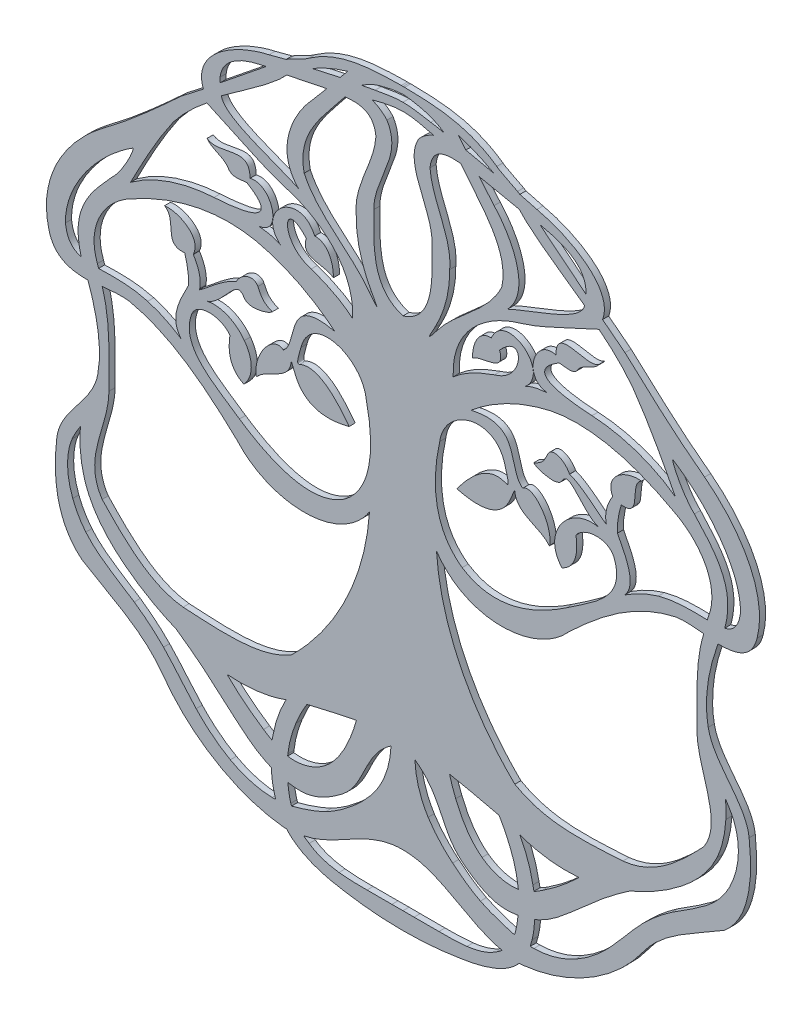
SolidWorks part; units mm, degrees
ref_plane "Front Plane" through (0, 0, 0) normal (0, 0, 1) x (1, 0, 0)
ref_plane "Top Plane" through (0, 0, 0) normal (0, 1, 0) x (1, 0, 0)
ref_plane "Right Plane" through (0, 0, 0) normal (1, 0, 0) x (0, 0, -1)
sketch "Sketch2" plane through (0, 0, 0) normal (0, 0, 1) x (1, 0, 0)
  line L0 (124.0467, 202.4567) -> (123.8762, 202.5007)
  line L1 (91.3206, 170.146) -> (91.46, 169.8814)
  line L2 (105.8644, 182.4526) -> (105.9481, 182.5183)
  line L3 (129.2501, 171.0909) -> (129.9283, 171.2663)
  line L4 (97.8903, 196.5004) -> (97.9848, 196.5477)
  line L5 (83.0151, 199.9226) -> (82.9279, 199.854)
  line L6 (67.6817, 189.4453) -> (67.9, 189.9835)
  line L7 (65.2474, 200.7194) -> (65.1856, 200.833)
  line L8 (61.6055, 199.6125) -> (61.6703, 199.4023)
  line L9 (180.5533, 202.4567) -> (180.7238, 202.5007)
  line L10 (213.2794, 170.146) -> (213.14, 169.8814)
  line L11 (198.7355, 182.4526) -> (198.6519, 182.5183)
  line L12 (175.3499, 171.0909) -> (174.6717, 171.2663)
  line L13 (206.7097, 196.5004) -> (206.6152, 196.5477)
  line L14 (221.5087, 199.9226) -> (221.5309, 199.9004)
  line L15 (236.8537, 189.6047) -> (236.6999, 189.9835)
  line L16 (239.3526, 200.7194) -> (239.4144, 200.833)
  line L17 (242.9945, 199.6125) -> (242.9297, 199.4023)
  line L18 (151.6258, 304.818) -> (152.3, 304.7699)
  line L19 (152.3, 304.7699) -> (152.9742, 304.818)
  line L20 (152.3, 8.2515) -> (147.7055, 8.2281)
  line L21 (156.8944, 8.2281) -> (152.3, 8.2515)
  line L22 (112.4054, 62.5359) -> (113.271, 62.7419)
  line L23 (192.1946, 62.5359) -> (191.329, 62.7419)
  spline S0 degree 3 poles (131.4175, 210.6535) (132.3447, 228.4153) (118.3052, 239.7229) (103.4832, 244.0034) knots 0 0 0 0 1 1 1 1
  spline S1 degree 3 poles (103.4832, 244.0034) (95.1251, 246.4171) (85.7701, 251.4597) (70.8553, 258.1318) knots 0 0 0 0 1 1 1 1
  spline S2 degree 3 poles (70.8553, 258.1318) (65.6236, 253.9512) (60.9556, 249.561) (56.9117, 244.3367) knots 0 0 0 0 1 1 1 1
  spline S3 degree 3 poles (56.9117, 244.3367) (50.1323, 234.6888) (44.4951, 224.0798) (39.129, 213.7146) knots 0 0 0 0 1 1 1 1
  spline S4 degree 3 poles (39.129, 213.7146) (49.1167, 221.0722) (61.6984, 224.9258) (73.7861, 225.6047) knots 0 0 0 0 1 1 1 1
  spline S5 degree 3 poles (73.7861, 225.6047) (81.1714, 226.0581) (104.1841, 227.716) (87.4693, 237.7349) knots 0 0 0 0 1 1 1 1
  spline S6 degree 3 poles (87.4693, 237.7349) (84.9969, 237.7465) (81.3851, 236.3748) (79.7778, 239.034) knots 0 0 0 0 1 1 1 1
  spline S7 degree 3 poles (79.7778, 239.034) (77.8345, 242.2491) (72.9741, 242.3849) (70.9297, 245.4413) knots 0 0 0 0 1 1 1 1
  spline S8 degree 3 poles (70.9297, 245.4413) (76.4954, 241.6186) (88.6993, 251.6059) (88.7661, 239.9743) knots 0 0 0 0 1 1 1 1
  spline S9 degree 3 poles (88.7661, 239.9743) (98.0513, 242.3534) (102.8069, 225.5) (92.2542, 224.5881) knots 0 0 0 0 1 1 1 1
  spline S10 degree 3 poles (92.2542, 224.5881) (95.4523, 224.2265) (98.8012, 223.862) (101.5143, 222.2107) knots 0 0 0 0 1 1 1 1
  spline S11 degree 3 poles (101.5143, 222.2107) (90.479, 231.7857) (109.6509, 246.2092) (115.6231, 232.6458) knots 0 0 0 0 1 1 1 1
  spline S12 degree 3 poles (115.6231, 232.6458) (121.3356, 232.927) (123.5816, 226.159) (123.3677, 221.4698) knots 0 0 0 0 1 1 1 1
  spline S13 degree 3 poles (123.3677, 221.4698) (119.7643, 224.5708) (109.41, 222.0646) (112.1698, 229.9921) knots 0 0 0 0 1 1 1 1
  spline S14 degree 3 poles (112.1698, 229.9921) (101.6543, 241.7817) (101.1203, 223.5384) (114.195, 220.0791) knots 0 0 0 0 1 1 1 1
  spline S15 degree 3 poles (114.195, 220.0791) (120.2811, 217.956) (126.7166, 215.0066) (131.5266, 210.6535) knots 0 0 0 0 1 1 1 1
  spline S16 degree 3 poles (173.1824, 210.6535) (172.2553, 228.4153) (186.2948, 239.7229) (201.1168, 244.0034) knots 0 0 0 0 1 1 1 1
  spline S17 degree 3 poles (201.1168, 244.0034) (209.4748, 246.4171) (218.8299, 251.4597) (233.7447, 258.1318) knots 0 0 0 0 1 1 1 1
  spline S18 degree 3 poles (233.7447, 258.1318) (238.9764, 253.9512) (243.6444, 249.561) (247.6883, 244.3367) knots 0 0 0 0 1 1 1 1
  spline S19 degree 3 poles (247.6883, 244.3367) (254.4677, 234.6888) (260.1049, 224.0798) (265.471, 213.7146) knots 0 0 0 0 1 1 1 1
  spline S20 degree 3 poles (265.471, 213.7146) (255.4833, 221.0722) (242.9016, 224.9258) (230.8139, 225.6047) knots 0 0 0 0 1 1 1 1
  spline S21 degree 3 poles (230.8139, 225.6047) (223.4286, 226.0581) (200.4159, 227.716) (217.1307, 237.7349) knots 0 0 0 0 1 1 1 1
  spline S22 degree 3 poles (217.1307, 237.7349) (219.6031, 237.7465) (223.2149, 236.3748) (224.8222, 239.034) knots 0 0 0 0 1 1 1 1
  spline S23 degree 3 poles (224.8222, 239.034) (226.7655, 242.2491) (231.6259, 242.3849) (233.6703, 245.4413) knots 0 0 0 0 1 1 1 1
  spline S24 degree 3 poles (233.6703, 245.4413) (228.1035, 241.6202) (215.9024, 251.6108) (215.8324, 239.9793) knots 0 0 0 0 1 1 1 1
  spline S25 degree 3 poles (215.8324, 239.9793) (206.5437, 242.3451) (201.8124, 225.4848) (212.3663, 224.5881) knots 0 0 0 0 1 1 1 1
  spline S26 degree 3 poles (212.3663, 224.5881) (209.1674, 224.2336) (205.8177, 223.8766) (203.101, 222.2314) knots 0 0 0 0 1 1 1 1
  spline S27 degree 3 poles (203.101, 222.2314) (214.1222, 231.8225) (194.9292, 246.218) (188.9769, 232.6458) knots 0 0 0 0 1 1 1 1
  spline S28 degree 3 poles (188.9769, 232.6458) (183.2643, 232.927) (181.0184, 226.159) (181.2323, 221.4698) knots 0 0 0 0 1 1 1 1
  spline S29 degree 3 poles (181.2323, 221.4698) (184.8357, 224.5708) (195.19, 222.0646) (192.4302, 229.9921) knots 0 0 0 0 1 1 1 1
  spline S30 degree 3 poles (192.4302, 229.9921) (202.9457, 241.7817) (203.4797, 223.5384) (190.405, 220.0791) knots 0 0 0 0 1 1 1 1
  spline S31 degree 3 poles (190.405, 220.0791) (184.3189, 217.956) (177.8834, 215.0066) (173.0734, 210.6535) knots 0 0 0 0 1 1 1 1
  spline S32 degree 3 poles (114.4335, 280.8354) (115.6926, 282.4321) (119.3612, 286.6279) (120.6433, 288.1846) knots 0 0 0 0 1 1 1 1
  spline S33 degree 3 poles (120.6433, 288.1846) (117.8502, 287.7388) (114.652, 286.9648) (111.6581, 286.3466) knots 0 0 0 0 1 1 1 1
  spline S34 degree 2 poles (111.6581, 286.3466) (109.0976, 285.8179) (103.9796, 284.7463) knots 0 0 0 1 1 1
  spline S35 degree 2 poles (103.9796, 284.7463) (101.9501, 282.7285) (101.0624, 281.7946) knots 0 0 0 1 1 1
  spline S36 degree 3 poles (101.0624, 281.7946) (93.5217, 275.03) (84.9819, 269.7463) (76.8684, 263.7279) knots 0 0 0 0 1 1 1 1
  spline S37 degree 3 poles (76.8684, 263.7279) (78.1012, 256.7056) (99.1504, 251.0771) (108.8436, 246.3864) knots 0 0 0 0 1 1 1 1
  spline S38 degree 3 poles (108.8436, 246.3864) (99.0563, 256.4976) (106.313, 272.0893) (114.4335, 280.8354) knots 0 0 0 0 1 1 1 1
  spline S39 degree 3 poles (190.1664, 280.8354) (188.9074, 282.4321) (185.2388, 286.6279) (183.9567, 288.1846) knots 0 0 0 0 1 1 1 1
  spline S40 degree 3 poles (183.9567, 288.1846) (186.7498, 287.7388) (189.948, 286.9648) (192.9419, 286.3466) knots 0 0 0 0 1 1 1 1
  spline S41 degree 2 poles (192.9419, 286.3466) (195.5024, 285.8179) (200.6204, 284.7463) knots 0 0 0 1 1 1
  spline S42 degree 2 poles (200.6204, 284.7463) (202.6498, 282.7285) (203.5376, 281.7946) knots 0 0 0 1 1 1
  spline S43 degree 3 poles (203.5376, 281.7946) (211.0783, 275.03) (219.6181, 269.7463) (227.7317, 263.7279) knots 0 0 0 0 1 1 1 1
  spline S44 degree 3 poles (227.7317, 263.7279) (226.4988, 256.7056) (205.4496, 251.0771) (195.7564, 246.3864) knots 0 0 0 0 1 1 1 1
  spline S45 degree 3 poles (195.7564, 246.3864) (205.5437, 256.4976) (198.287, 272.0893) (190.1664, 280.8354) knots 0 0 0 0 1 1 1 1
  spline S46 degree 3 poles (129.3371, 298.7606) (124.328, 297.3007) (119.1122, 295.0858) (114.5869, 292.4347) knots 0 0 0 0 1 1 1 1
  spline S47 degree 3 poles (114.5869, 292.4347) (114.6743, 292.3899) (114.9619, 292.4909) (115.0634, 292.5134) knots 0 0 0 0 1 1 1 1
  spline S48 degree 3 poles (115.0634, 292.5134) (118.7134, 293.3211) (122.4339, 294.1357) (126.1731, 294.9789) knots 0 0 0 0 1 1 1 1
  spline S49 degree 3 poles (126.1731, 294.9789) (127.3382, 296.4139) (128.2034, 297.377) (129.3371, 298.7606) knots 0 0 0 0 1 1 1 1
  spline S50 degree 3 poles (175.2629, 298.7606) (180.272, 297.3007) (185.4878, 295.0858) (190.0131, 292.4347) knots 0 0 0 0 1 1 1 1
  spline S51 degree 3 poles (190.0131, 292.4347) (189.9257, 292.3899) (189.6381, 292.4909) (189.5365, 292.5134) knots 0 0 0 0 1 1 1 1
  spline S52 degree 3 poles (189.5365, 292.5134) (185.8866, 293.3211) (182.1661, 294.1357) (178.4269, 294.9789) knots 0 0 0 0 1 1 1 1
  spline S53 degree 3 poles (178.4269, 294.9789) (177.2618, 296.4139) (176.3966, 297.377) (175.2629, 298.7606) knots 0 0 0 0 1 1 1 1
  spline S54 degree 3 poles (152.3, 299.1254) (148.3241, 299.1244) (144.6166, 298.3006) (140.731, 297.6643) knots 0 0 0 0 1 1 1 1
  spline S55 degree 3 poles (140.731, 297.6643) (138.8136, 297.3503) (136.9533, 297.0896) (135.1322, 296.6129) knots 0 0 0 0 1 1 1 1
  spline S56 degree 3 poles (135.1322, 296.6129) (137.3724, 298.1704) (139.9061, 299.5052) (142.8771, 300.2975) knots 0 0 0 0 1 1 1 1
  spline S57 degree 3 poles (142.8771, 300.2975) (145.4603, 300.9863) (149.2794, 301.9033) (152.3, 301.9499) knots 0 0 0 0 1 1 1 1
  spline S58 degree 3 poles (152.3, 301.9499) (155.3206, 301.9033) (159.1397, 300.9863) (161.7229, 300.2975) knots 0 0 0 0 1 1 1 1
  spline S59 degree 3 poles (161.7229, 300.2975) (164.6939, 299.5052) (167.2275, 298.1704) (169.4678, 296.6129) knots 0 0 0 0 1 1 1 1
  spline S60 degree 3 poles (169.4678, 296.6129) (167.6467, 297.0896) (165.7864, 297.3503) (163.869, 297.6643) knots 0 0 0 0 1 1 1 1
  spline S61 degree 3 poles (163.869, 297.6643) (159.9834, 298.3006) (156.2759, 299.1244) (152.3, 299.1254) knots 0 0 0 0 1 1 1 1
  spline S62 degree 2 poles (127.5425, 288.1624) (128.1065, 289.0471) (128.5638, 289.0858) knots 0 0 0 1 1 1
  spline S63 degree 3 poles (128.5638, 289.0858) (133.4843, 289.5017) (140.2137, 289.6551) (141.0643, 281.1364) knots 0 0 0 0 1 1 1 1
  spline S64 degree 3 poles (141.0643, 281.1364) (140.1847, 269.7923) (131.7735, 260.4078) (132.895, 248.5982) knots 0 0 0 0 1 1 1 1
  spline S65 degree 3 poles (132.895, 248.5982) (132.7464, 240.2776) (135.0817, 232.1131) (139.0246, 224.7742) knots 0 0 0 0 1 1 1 1
  spline S66 degree 3 poles (139.0246, 224.7742) (139.9951, 222.9677) (140.9599, 221.4257) (141.503, 220.1266) knots 0 0 0 0 1 1 1 1
  spline S67 degree 3 poles (141.503, 220.1266) (140.3841, 220.9726) (138.7592, 223.2318) (138.373, 223.7558) knots 0 0 0 0 1 1 1 1
  spline S68 degree 3 poles (138.373, 223.7558) (130.4207, 234.5457) (117.0074, 240.7506) (111.2689, 253.0797) knots 0 0 0 0 1 1 1 1
  spline S69 degree 3 poles (111.2689, 253.0797) (108.114, 267.1941) (119.5485, 277.7332) (127.5425, 288.1624) knots 0 0 0 0 1 1 1 1
  spline S70 degree 2 poles (177.0575, 288.1624) (176.4935, 289.0471) (176.0362, 289.0858) knots 0 0 0 1 1 1
  spline S71 degree 3 poles (176.0362, 289.0858) (171.1157, 289.5017) (164.3863, 289.6551) (163.5357, 281.1364) knots 0 0 0 0 1 1 1 1
  spline S72 degree 3 poles (163.5357, 281.1364) (164.4153, 269.7923) (172.8265, 260.4078) (171.705, 248.5982) knots 0 0 0 0 1 1 1 1
  spline S73 degree 3 poles (171.705, 248.5982) (171.8536, 240.2776) (169.5183, 232.1131) (165.5754, 224.7742) knots 0 0 0 0 1 1 1 1
  spline S74 degree 3 poles (165.5754, 224.7742) (164.6049, 222.9677) (163.6401, 221.4257) (163.097, 220.1266) knots 0 0 0 0 1 1 1 1
  spline S75 degree 3 poles (163.097, 220.1266) (164.2159, 220.9726) (165.8408, 223.2318) (166.227, 223.7558) knots 0 0 0 0 1 1 1 1
  spline S76 degree 3 poles (166.227, 223.7558) (174.1793, 234.5457) (187.5926, 240.7506) (193.3311, 253.0797) knots 0 0 0 0 1 1 1 1
  spline S77 degree 3 poles (193.3311, 253.0797) (196.486, 267.1941) (185.0515, 277.7332) (177.0575, 288.1624) knots 0 0 0 0 1 1 1 1
  spline S78 degree 3 poles (152.3, 295.8123) (148.0396, 295.8206) (143.6999, 294.6762) (139.5652, 293.5948) knots 0 0 0 0 1 1 1 1
  spline S79 degree 3 poles (139.5652, 293.5948) (141.8404, 292.6266) (144.0165, 291.2342) (145.6385, 289.3762) knots 0 0 0 0 1 1 1 1
  spline S80 degree 3 poles (145.6385, 289.3762) (152.4254, 278.2423) (139.9784, 266.2911) (140.2295, 254.4964) knots 0 0 0 0 1 1 1 1
  spline S81 degree 3 poles (140.2295, 254.4964) (140.1957, 243.0196) (138.6463, 226.432) (152.3, 222.2438) knots 0 0 0 0 1 1 1 1
  spline S82 degree 3 poles (152.3, 222.2438) (165.9537, 226.432) (164.4042, 243.0196) (164.3705, 254.4964) knots 0 0 0 0 1 1 1 1
  spline S83 degree 3 poles (164.3705, 254.4964) (164.6216, 266.2911) (152.1746, 278.2423) (158.9614, 289.3762) knots 0 0 0 0 1 1 1 1
  spline S84 degree 3 poles (158.9614, 289.3762) (160.5835, 291.2342) (162.7595, 292.6266) (165.0348, 293.5948) knots 0 0 0 0 1 1 1 1
  spline S85 degree 3 poles (165.0348, 293.5948) (160.9, 294.6762) (156.5604, 295.8206) (152.3, 295.8123) knots 0 0 0 0 1 1 1 1
  spline S86 degree 3 poles (138.393, 144.7648) (136.7141, 119.0567) (124.1429, 94.7808) (105.8412, 76.9863) knots 0 0 0 0 1 1 1 1
  spline S87 degree 3 poles (105.8412, 76.9863) (92.5807, 69.194) (75.7737, 71.0297) (60.9563, 71.7833) knots 0 0 0 0 1 1 1 1
  spline S88 degree 3 poles (60.9563, 71.7833) (47.0886, 73.2325) (36.4636, 84.1427) (27.3496, 93.7397) knots 0 0 0 0 1 1 1 1
  spline S89 degree 3 poles (27.3496, 93.7397) (18.9888, 106.169) (30.1727, 120.5622) (30.1207, 134.0209) knots 0 0 0 0 1 1 1 1
  spline S90 degree 3 poles (30.1207, 134.0209) (30.0733, 146.1697) (31.0468, 158.3956) (27.3371, 170.3611) knots 0 0 0 0 1 1 1 1
  spline S91 degree 3 poles (27.3371, 170.3611) (31.3099, 170.7994) (34.97, 171.0964) (38.5956, 170.6815) knots 0 0 0 0 1 1 1 1
  spline S92 degree 3 poles (38.5956, 170.6815) (56.2045, 166.9376) (70.5686, 155.1577) (83.3766, 143.055) knots 0 0 0 0 1 1 1 1
  spline S93 degree 3 poles (83.3766, 143.055) (97.3136, 127.266) (126.3061, 126.2979) (138.393, 144.7648) knots 0 0 0 0 1 1 1 1
  spline S94 degree 3 poles (166.207, 144.7648) (167.8858, 119.0568) (180.4571, 94.7808) (198.7588, 76.9863) knots 0 0 0 0 1 1 1 1
  spline S95 degree 3 poles (198.7588, 76.9863) (212.0192, 69.1941) (228.8263, 71.0297) (243.6437, 71.7833) knots 0 0 0 0 1 1 1 1
  spline S96 degree 3 poles (243.6437, 71.7833) (257.5114, 73.2325) (268.1364, 84.1427) (277.2504, 93.7397) knots 0 0 0 0 1 1 1 1
  spline S97 degree 3 poles (277.2504, 93.7397) (285.6111, 106.169) (274.4273, 120.5622) (274.4792, 134.021) knots 0 0 0 0 1 1 1 1
  spline S98 degree 3 poles (274.4792, 134.021) (274.5267, 146.1698) (273.5532, 158.3956) (277.2629, 170.3611) knots 0 0 0 0 1 1 1 1
  spline S99 degree 3 poles (277.2629, 170.3611) (273.29, 170.7995) (269.63, 171.0965) (266.0043, 170.6816) knots 0 0 0 0 1 1 1 1
  spline S100 degree 3 poles (266.0043, 170.6816) (248.3955, 166.9376) (234.0314, 155.1577) (221.2233, 143.055) knots 0 0 0 0 1 1 1 1
  spline S101 degree 3 poles (221.2233, 143.055) (207.2864, 127.2661) (178.2939, 126.298) (166.207, 144.7648) knots 0 0 0 0 1 1 1 1
  spline S102 degree 3 poles (46.2351, 174.4703) (39.6791, 176.3428) (32.8481, 176.302) (25.8444, 176.084) knots 0 0 0 0 1 1 1 1
  spline S103 degree 3 poles (25.8444, 176.084) (25.679, 176.6138) (25.5192, 177.1739) (25.3574, 177.6166) knots 0 0 0 0 1 1 1 1
  spline S104 degree 3 poles (25.3574, 177.6166) (20.6372, 190.1004) (28.508, 202.3386) (39.5126, 207.9637) knots 0 0 0 0 1 1 1 1
  spline S105 degree 3 poles (39.5126, 207.9637) (56.5344, 217.5028) (77.3037, 223.5116) (96.5267, 217.2946) knots 0 0 0 0 1 1 1 1
  spline S106 degree 3 poles (96.5267, 217.2946) (106.604, 214.3435) (115.9871, 209.1659) (124.0467, 202.4567) knots 0 0 0 0 1 1 1 1
  spline S107 degree 3 poles (123.8762, 202.5007) (102.8617, 207.2096) (109.0778, 189.8912) (102.5829, 185.1128) knots 0 0 0 0 1 1 1 1
  spline S108 degree 3 poles (102.5829, 185.1128) (98.498, 188.7463) (90.1011, 178.3426) (91.3206, 170.146) knots 0 0 0 0 1 1 1 1
  spline S109 degree 3 poles (91.46, 169.8814) (95.4825, 174.8633) (105.0198, 174.7206) (105.8644, 182.4526) knots 0 0 0 0 1 1 1 1
  spline S110 degree 3 poles (105.9481, 182.5183) (107.3696, 180.8372) (108.6578, 165.9257) (129.2501, 171.0909) knots 0 0 0 0 1 1 1 1
  spline S111 degree 3 poles (129.9283, 171.2663) (118.3183, 187.2048) (111.5062, 184.15) (109.3456, 183.319) knots 0 0 0 0 1 1 1 1
  spline S112 degree 3 poles (109.3456, 183.319) (107.8132, 182.7296) (108.8287, 185.5642) (109.8908, 189.6794) knots 0 0 0 0 1 1 1 1
  spline S113 degree 3 poles (109.8908, 189.6794) (114.0597, 205.4698) (135.1768, 198.7623) (137.0165, 184.7176) knots 0 0 0 0 1 1 1 1
  spline S114 degree 3 poles (137.0165, 184.7176) (140.137, 170.9477) (140.6245, 153.1114) (127.7174, 143.9936) knots 0 0 0 0 1 1 1 1
  spline S115 degree 3 poles (127.7174, 143.9936) (113.833, 134.8827) (96.5984, 142.9299) (84.3693, 151.1929) knots 0 0 0 0 1 1 1 1
  spline S116 degree 3 poles (84.3693, 151.1929) (75.1853, 157.8988) (59.2294, 165.1485) (64.5923, 179.0979) knots 0 0 0 0 1 1 1 1
  spline S117 degree 3 poles (64.5923, 179.0979) (66.9538, 184.9307) (77.0091, 184.1136) (80.4255, 179.3261) knots 0 0 0 0 1 1 1 1
  spline S118 degree 3 poles (80.4255, 179.3261) (79.5564, 174.0329) (80.0248, 167.4336) (86.2486, 164.6464) knots 0 0 0 0 1 1 1 1
  spline S119 degree 3 poles (86.2486, 164.6464) (90.7064, 169.5764) (89.8124, 175.7936) (86.4154, 180.4431) knots 0 0 0 0 1 1 1 1
  spline S120 degree 3 poles (86.4154, 180.4431) (83.0185, 185.0927) (77.0524, 188.0567) (71.2147, 186.8881) knots 0 0 0 0 1 1 1 1
  spline S121 degree 3 poles (71.2147, 186.8881) (71.1722, 186.9645) (71.196, 186.972) (71.2196, 186.98) knots 0 0 0 0 1 1 1 1
  spline S122 degree 3 poles (71.2196, 186.98) (76.5759, 188.7809) (81.166, 197.5957) (84.3777, 197.5398) knots 0 0 0 0 1 1 1 1
  spline S123 degree 3 poles (84.3777, 197.5398) (85.4432, 197.0727) (85.8768, 196.6453) (86.1714, 196.0093) knots 0 0 0 0 1 1 1 1
  spline S124 degree 3 poles (86.1714, 196.0093) (86.5689, 195.1511) (87.5991, 194.5447) (88.8676, 194.3007) knots 0 0 0 0 1 1 1 1
  spline S125 degree 3 poles (88.8676, 194.3007) (90.8614, 193.9173) (96.1705, 194.8484) (97.8903, 196.5004) knots 0 0 0 0 1 1 1 1
  spline S126 degree 3 poles (97.9848, 196.5477) (93.825, 198.287) (93.3525, 200.0284) (92.0174, 202.6889) knots 0 0 0 0 1 1 1 1
  spline S127 degree 3 poles (92.0174, 202.6889) (90.3752, 205.8774) (85.293, 204.1872) (83.0151, 199.9226) knots 0 0 0 0 1 1 1 1
  spline S128 degree 3 poles (82.9279, 199.854) (76.824, 197.7238) (67.801, 188.5865) (67.6817, 189.4453) knots 0 0 0 0 1 1 1 1
  spline S129 degree 3 poles (67.9, 189.9835) (68.5673, 193.7333) (67.2708, 197.494) (65.2474, 200.7194) knots 0 0 0 0 1 1 1 1
  spline S130 degree 3 poles (65.1856, 200.833) (68.6792, 208.0434) (59.3068, 213.1619) (53.2336, 212.3406) knots 0 0 0 0 1 1 1 1
  spline S131 degree 3 poles (53.2336, 212.3406) (58.5733, 209.4882) (52.3668, 198.6152) (61.6055, 199.6125) knots 0 0 0 0 1 1 1 1
  spline S132 degree 3 poles (61.6703, 199.4023) (62.7171, 195.8296) (63.4337, 192.3982) (63.1786, 188.6295) knots 0 0 0 0 1 1 1 1
  spline S133 degree 3 poles (63.1786, 188.6295) (60.8737, 184.2306) (57.3543, 178.0162) (58.0001, 172.7835) knots 0 0 0 0 1 1 1 1
  spline S134 degree 3 poles (58.0001, 172.7835) (58.211, 171.0746) (58.8662, 169.4704) (60.1704, 167.9309) knots 0 0 0 0 1 1 1 1
  spline S135 degree 3 poles (60.1704, 167.9309) (55.7976, 170.7602) (51.2465, 173.039) (46.2351, 174.4703) knots 0 0 0 0 1 1 1 1
  spline S136 degree 3 poles (258.3648, 174.4703) (264.9209, 176.3428) (271.7519, 176.302) (278.7556, 176.084) knots 0 0 0 0 1 1 1 1
  spline S137 degree 3 poles (278.7556, 176.084) (278.921, 176.6138) (279.0808, 177.1739) (279.2426, 177.6166) knots 0 0 0 0 1 1 1 1
  spline S138 degree 3 poles (279.2426, 177.6166) (283.9628, 190.1004) (276.092, 202.3386) (265.0874, 207.9637) knots 0 0 0 0 1 1 1 1
  spline S139 degree 3 poles (265.0874, 207.9637) (248.0656, 217.5028) (227.2963, 223.5116) (208.0732, 217.2946) knots 0 0 0 0 1 1 1 1
  spline S140 degree 3 poles (208.0732, 217.2946) (197.996, 214.3435) (188.6129, 209.1659) (180.5533, 202.4567) knots 0 0 0 0 1 1 1 1
  spline S141 degree 3 poles (180.7238, 202.5007) (201.7383, 207.2096) (195.5222, 189.8912) (202.0171, 185.1128) knots 0 0 0 0 1 1 1 1
  spline S142 degree 3 poles (202.0171, 185.1128) (206.102, 188.7463) (214.4989, 178.3426) (213.2794, 170.146) knots 0 0 0 0 1 1 1 1
  spline S143 degree 3 poles (213.14, 169.8814) (209.1174, 174.8633) (199.5802, 174.7206) (198.7355, 182.4526) knots 0 0 0 0 1 1 1 1
  spline S144 degree 3 poles (198.6519, 182.5183) (197.2303, 180.8372) (195.9422, 165.9257) (175.3499, 171.0909) knots 0 0 0 0 1 1 1 1
  spline S145 degree 3 poles (174.6717, 171.2663) (186.2817, 187.2048) (193.0938, 184.15) (195.2544, 183.319) knots 0 0 0 0 1 1 1 1
  spline S146 degree 3 poles (195.2544, 183.319) (196.7868, 182.7296) (195.7713, 185.5642) (194.7091, 189.6794) knots 0 0 0 0 1 1 1 1
  spline S147 degree 3 poles (194.7091, 189.6794) (190.5402, 205.4698) (169.4232, 198.7623) (167.5835, 184.7176) knots 0 0 0 0 1 1 1 1
  spline S148 degree 3 poles (167.5835, 184.7176) (164.463, 170.9477) (163.9755, 153.1114) (176.8825, 143.9936) knots 0 0 0 0 1 1 1 1
  spline S149 degree 3 poles (176.8825, 143.9936) (190.767, 134.8827) (208.0016, 142.9299) (220.2307, 151.1929) knots 0 0 0 0 1 1 1 1
  spline S150 degree 3 poles (220.2307, 151.1929) (229.4147, 157.8988) (245.3706, 165.1485) (240.0077, 179.0979) knots 0 0 0 0 1 1 1 1
  spline S151 degree 3 poles (240.0077, 179.0979) (237.6462, 184.9307) (227.5909, 184.1136) (224.1745, 179.3261) knots 0 0 0 0 1 1 1 1
  spline S152 degree 3 poles (224.1745, 179.3261) (225.0436, 174.0329) (224.5752, 167.4336) (218.3513, 164.6464) knots 0 0 0 0 1 1 1 1
  spline S153 degree 3 poles (218.3513, 164.6464) (213.8936, 169.5764) (214.7876, 175.7936) (218.1846, 180.4431) knots 0 0 0 0 1 1 1 1
  spline S154 degree 3 poles (218.1846, 180.4431) (221.5815, 185.0927) (227.5476, 188.0567) (233.3853, 186.8881) knots 0 0 0 0 1 1 1 1
  spline S155 degree 3 poles (233.3853, 186.8881) (233.4277, 186.9645) (233.404, 186.972) (233.3803, 186.98) knots 0 0 0 0 1 1 1 1
  spline S156 degree 3 poles (233.3803, 186.98) (228.0241, 188.7809) (223.434, 197.5957) (220.2223, 197.5398) knots 0 0 0 0 1 1 1 1
  spline S157 degree 3 poles (220.2223, 197.5398) (219.1568, 197.0727) (218.7232, 196.6453) (218.4286, 196.0093) knots 0 0 0 0 1 1 1 1
  spline S158 degree 3 poles (218.4286, 196.0093) (218.0311, 195.1511) (217.0009, 194.5447) (215.7324, 194.3007) knots 0 0 0 0 1 1 1 1
  spline S159 degree 3 poles (215.7324, 194.3007) (213.7386, 193.9173) (208.4295, 194.8484) (206.7097, 196.5004) knots 0 0 0 0 1 1 1 1
  spline S160 degree 3 poles (206.6152, 196.5477) (210.7583, 198.3264) (211.2142, 200.0723) (212.5239, 202.7453) knots 0 0 0 0 1 1 1 1
  spline S161 degree 3 poles (212.5239, 202.7453) (214.1861, 205.9235) (219.2576, 204.2014) (221.5087, 199.9226) knots 0 0 0 0 1 1 1 1
  spline S162 degree 3 poles (221.5309, 199.9004) (227.6504, 197.8155) (236.7406, 188.745) (236.8537, 189.6047) knots 0 0 0 0 1 1 1 1
  spline S163 degree 3 poles (236.6999, 189.9835) (236.0327, 193.7333) (237.3292, 197.494) (239.3526, 200.7194) knots 0 0 0 0 1 1 1 1
  spline S164 degree 3 poles (239.4144, 200.833) (235.9208, 208.0434) (245.2932, 213.1619) (251.3664, 212.3406) knots 0 0 0 0 1 1 1 1
  spline S165 degree 3 poles (251.3664, 212.3406) (246.0267, 209.4882) (252.2332, 198.6152) (242.9945, 199.6125) knots 0 0 0 0 1 1 1 1
  spline S166 degree 3 poles (242.9297, 199.4023) (241.8829, 195.8296) (241.1663, 192.3982) (241.4213, 188.6295) knots 0 0 0 0 1 1 1 1
  spline S167 degree 3 poles (241.4213, 188.6295) (244.5066, 182.7413) (249.7681, 173.6) (244.3513, 167.8557) knots 0 0 0 0 1 1 1 1
  spline S168 degree 3 poles (244.3513, 167.8557) (248.7939, 170.7648) (253.3488, 173.0376) (258.3648, 174.4703) knots 0 0 0 0 1 1 1 1
  spline S169 degree 3 poles (12.0828, 185.5873) (11.7558, 200.4537) (26.0775, 217.7236) (39.8702, 226.3689) knots 0 0 0 0 1 1 1 1
  spline S170 degree 3 poles (39.8702, 226.3689) (41.6172, 228.106) (36.7474, 216.6331) (31.2383, 211.5411) knots 0 0 0 0 1 1 1 1
  spline S171 degree 3 poles (31.2383, 211.5411) (21.5263, 201.0771) (14.3143, 192.3625) (18.6256, 176.7103) knots 0 0 0 0 1 1 1 1
  spline S172 degree 3 poles (18.6256, 176.7103) (15.193, 177.5037) (12.7536, 179.9668) (12.0828, 185.5873) knots 0 0 0 0 1 1 1 1
  spline S173 degree 3 poles (292.5172, 185.5873) (292.8441, 200.4537) (278.5225, 217.7236) (264.7298, 226.3689) knots 0 0 0 0 1 1 1 1
  spline S174 degree 3 poles (264.7298, 226.3689) (262.9827, 228.106) (267.8526, 216.6331) (273.3617, 211.5411) knots 0 0 0 0 1 1 1 1
  spline S175 degree 3 poles (273.3617, 211.5411) (283.0737, 201.0771) (290.2856, 192.3625) (285.9744, 176.7103) knots 0 0 0 0 1 1 1 1
  spline S176 degree 3 poles (285.9744, 176.7103) (289.407, 177.5037) (291.8464, 179.9668) (292.5172, 185.5873) knots 0 0 0 0 1 1 1 1
  spline S177 degree 3 poles (152.3, 1.0542) (149.3587, 1.0522) (146.2599, 1.137) (143.3042, 1.323) knots 0 0 0 0 1 1 1 1
  spline S178 degree 3 poles (143.3042, 1.323) (138.2526, 1.6411) (133.2211, 2.2444) (128.2229, 3.0428) knots 0 0 0 0 1 1 1 1
  spline S179 degree 3 poles (128.2229, 3.0428) (123.5579, 3.788) (118.8862, 4.7132) (114.5072, 6.4858) knots 0 0 0 0 1 1 1 1
  spline S180 degree 3 poles (114.5072, 6.4858) (110.4914, 8.1114) (106.7891, 10.2032) (103.9591, 13.5029) knots 0 0 0 0 1 1 1 1
  spline S181 degree 3 poles (103.9591, 13.5029) (103.4639, 13.5462) (102.8533, 13.5009) (102.3689, 13.5532) knots 0 0 0 0 1 1 1 1
  spline S182 degree 3 poles (102.3689, 13.5532) (83.2086, 15.6221) (64.1309, 27.0358) (52.6722, 43.0965) knots 0 0 0 0 1 1 1 1
  spline S183 degree 3 poles (52.6722, 43.0965) (44.2613, 55.0397) (30.7505, 60.4837) (18.9079, 67.87) knots 0 0 0 0 1 1 1 1
  spline S184 degree 3 poles (18.9079, 67.87) (7.7221, 76.9854) (6.9268, 93.1764) (8.4785, 106.3869) knots 0 0 0 0 1 1 1 1
  spline S185 degree 3 poles (8.4785, 106.3869) (9.8627, 118.171) (23.2932, 125.994) (25.4902, 137.654) knots 0 0 0 0 1 1 1 1
  spline S186 degree 3 poles (25.4902, 137.654) (27.4822, 148.2261) (25.1143, 159.333) (21.4405, 169.6735) knots 0 0 0 0 1 1 1 1
  spline S187 degree 3 poles (21.4405, 169.6735) (14.0929, 169.6188) (7.3094, 171.1538) (5.1986, 179.7976) knots 0 0 0 0 1 1 1 1
  spline S188 degree 3 poles (5.1986, 179.7976) (0.4768, 198.2467) (12.9432, 216.166) (27.006, 226.9131) knots 0 0 0 0 1 1 1 1
  spline S189 degree 3 poles (27.006, 226.9131) (38.7004, 235.5525) (49.414, 245.3115) (60.0737, 255.1498) knots 0 0 0 0 1 1 1 1
  spline S190 degree 3 poles (60.0737, 255.1498) (63.0584, 257.6132) (66.2, 259.7648) (69.3755, 262.3803) knots 0 0 0 0 1 1 1 1
  spline S191 degree 3 poles (69.3755, 262.3803) (64.5839, 275.4394) (83.7948, 285.6417) (96.666, 288.368) knots 0 0 0 0 1 1 1 1
  spline S192 degree 3 poles (96.666, 288.368) (98.935, 288.8486) (101.2604, 289.7003) (103.7402, 290.2368) knots 0 0 0 0 1 1 1 1
  spline S193 degree 3 poles (103.7402, 290.2368) (103.8864, 290.3272) (104.3899, 290.6453) (104.7223, 290.8366) knots 0 0 0 0 1 1 1 1
  spline S194 degree 3 poles (104.7223, 290.8366) (107.5513, 292.4651) (111.5848, 294.1033) (113.3332, 295.5002) knots 0 0 0 0 1 1 1 1
  spline S195 degree 3 poles (113.3332, 295.5002) (124.9781, 303.8314) (137.6751, 304.65) (151.6258, 304.818) knots 0 0 0 0 1 1 1 1
  spline S196 degree 3 poles (152.9742, 304.818) (166.9249, 304.65) (179.6219, 303.8314) (191.2668, 295.5002) knots 0 0 0 0 1 1 1 1
  spline S197 degree 3 poles (191.2668, 295.5002) (193.0152, 294.1033) (197.0487, 292.4651) (199.8777, 290.8366) knots 0 0 0 0 1 1 1 1
  spline S198 degree 3 poles (199.8777, 290.8366) (200.2101, 290.6453) (200.7136, 290.3272) (200.8598, 290.2368) knots 0 0 0 0 1 1 1 1
  spline S199 degree 3 poles (200.8598, 290.2368) (203.3396, 289.7003) (205.665, 288.8486) (207.934, 288.368) knots 0 0 0 0 1 1 1 1
  spline S200 degree 3 poles (207.934, 288.368) (220.8052, 285.6417) (240.0161, 275.4394) (235.2245, 262.3803) knots 0 0 0 0 1 1 1 1
  spline S201 degree 3 poles (235.2245, 262.3803) (238.4, 259.7648) (241.5416, 257.6132) (244.5263, 255.1498) knots 0 0 0 0 1 1 1 1
  spline S202 degree 3 poles (244.5263, 255.1498) (255.186, 245.3115) (265.8996, 235.5525) (277.594, 226.9131) knots 0 0 0 0 1 1 1 1
  spline S203 degree 3 poles (277.594, 226.9131) (291.6568, 216.166) (304.1232, 198.2467) (299.4014, 179.7976) knots 0 0 0 0 1 1 1 1
  spline S204 degree 3 poles (299.4014, 179.7976) (297.2905, 171.1538) (290.5071, 169.6188) (283.1595, 169.6735) knots 0 0 0 0 1 1 1 1
  spline S205 degree 3 poles (283.1595, 169.6735) (279.4858, 159.333) (277.1178, 148.2261) (279.1098, 137.654) knots 0 0 0 0 1 1 1 1
  spline S206 degree 3 poles (279.1098, 137.654) (281.3068, 125.994) (294.7373, 118.171) (296.1214, 106.3869) knots 0 0 0 0 1 1 1 1
  spline S207 degree 3 poles (296.1214, 106.3869) (297.6732, 93.1764) (296.8779, 76.9854) (285.6921, 67.87) knots 0 0 0 0 1 1 1 1
  spline S208 degree 3 poles (285.6921, 67.87) (273.8494, 60.4837) (260.3387, 55.0397) (251.9278, 43.0965) knots 0 0 0 0 1 1 1 1
  spline S209 degree 3 poles (251.9278, 43.0965) (240.4691, 27.0358) (221.3914, 15.6221) (202.2311, 13.5532) knots 0 0 0 0 1 1 1 1
  spline S210 degree 3 poles (202.2311, 13.5532) (201.7467, 13.5009) (201.1361, 13.5462) (200.6409, 13.5029) knots 0 0 0 0 1 1 1 1
  spline S211 degree 3 poles (200.6409, 13.5029) (197.8109, 10.2032) (194.1086, 8.1114) (190.0928, 6.4858) knots 0 0 0 0 1 1 1 1
  spline S212 degree 3 poles (190.0928, 6.4858) (185.7138, 4.7132) (181.0421, 3.788) (176.3771, 3.0428) knots 0 0 0 0 1 1 1 1
  spline S213 degree 3 poles (176.3771, 3.0428) (171.3789, 2.2444) (166.3474, 1.6411) (161.2958, 1.323) knots 0 0 0 0 1 1 1 1
  spline S214 degree 3 poles (161.2958, 1.323) (158.3401, 1.1369) (155.2413, 1.0525) (152.3, 1.0542) knots 0 0 0 0 1 1 1 1
  spline S215 degree 3 poles (95.2531, 283.378) (95.2309, 283.5123) (95.2093, 283.5083) (95.1876, 283.5042) knots 0 0 0 0 1 1 1 1
  spline S216 degree 3 poles (95.1876, 283.5042) (85.8929, 281.761) (77.2182, 278.0248) (76.3484, 270.194) knots 0 0 0 0 1 1 1 1
  spline S217 degree 3 poles (76.3484, 270.194) (76.2785, 269.565) (76.2594, 268.7781) (76.3115, 268.107) knots 0 0 0 0 1 1 1 1
  spline S218 degree 3 poles (76.3115, 268.107) (82.6506, 273.1515) (88.7843, 278.2084) (95.2531, 283.378) knots 0 0 0 0 1 1 1 1
  spline S219 degree 3 poles (209.3468, 283.378) (209.3691, 283.5123) (209.3907, 283.5083) (209.4123, 283.5042) knots 0 0 0 0 1 1 1 1
  spline S220 degree 3 poles (209.4123, 283.5042) (218.7071, 281.761) (227.3818, 278.0248) (228.2516, 270.194) knots 0 0 0 0 1 1 1 1
  spline S221 degree 3 poles (228.2516, 270.194) (228.3215, 269.565) (228.3406, 268.7781) (228.2884, 268.107) knots 0 0 0 0 1 1 1 1
  spline S222 degree 3 poles (228.2884, 268.107) (221.9493, 273.1515) (215.8156, 278.2084) (209.3468, 283.378) knots 0 0 0 0 1 1 1 1
  spline S223 degree 3 poles (18.1563, 108.1484) (18.4568, 102.7769) (19.6002, 97.4202) (21.8604, 92.538) knots 0 0 0 0 1 1 1 1
  spline S224 degree 3 poles (21.8604, 92.538) (25.0728, 85.5993) (30.4308, 79.8384) (36.4125, 75.0755) knots 0 0 0 0 1 1 1 1
  spline S225 degree 3 poles (36.4125, 75.0755) (42.9607, 69.8615) (50.3255, 65.7179) (58.0619, 62.4519) knots 0 0 0 0 1 1 1 1
  spline S226 degree 3 poles (58.0619, 62.4519) (61.9791, 59.7818) (65.7581, 56.9601) (69.4034, 53.9751) knots 0 0 0 0 1 1 1 1
  spline S227 degree 3 poles (69.4034, 53.9751) (73.97, 50.2357) (78.3226, 46.2441) (82.7803, 42.3756) knots 0 0 0 0 1 1 1 1
  spline S228 degree 3 poles (82.7803, 42.3756) (86.6648, 39.0045) (90.6805, 35.6932) (95.3066, 33.4454) knots 0 0 0 0 1 1 1 1
  spline S229 degree 3 poles (95.3066, 33.4454) (96.017, 33.1003) (96.7441, 32.7579) (97.5824, 32.4747) knots 0 0 0 0 1 1 1 1
  spline S230 degree 3 poles (97.5824, 32.4747) (97.6806, 29.732) (98.0485, 27.1286) (98.6557, 24.6063) knots 0 0 0 0 1 1 1 1
  spline S231 degree 3 poles (98.6557, 24.6063) (98.8531, 23.7862) (99.1466, 22.8141) (99.4315, 21.844) knots 0 0 0 0 1 1 1 1
  spline S232 degree 3 poles (99.4315, 21.844) (98.961, 21.8112) (98.4075, 21.8224) (97.9281, 21.8283) knots 0 0 0 0 1 1 1 1
  spline S233 degree 3 poles (97.9281, 21.8283) (91.8599, 21.9006) (85.8885, 23.7595) (80.5721, 26.6861) knots 0 0 0 0 1 1 1 1
  spline S234 degree 3 poles (80.5721, 26.6861) (75.2558, 29.6125) (70.5659, 33.5818) (66.3868, 37.9822) knots 0 0 0 0 1 1 1 1
  spline S235 degree 3 poles (66.3868, 37.9822) (61.6856, 42.9322) (57.5978, 48.4421) (52.8261, 53.3241) knots 0 0 0 0 1 1 1 1
  spline S236 degree 3 poles (52.8261, 53.3241) (49.1221, 57.1137) (45.0197, 60.5085) (40.6458, 63.5) knots 0 0 0 0 1 1 1 1
  spline S237 degree 3 poles (40.6458, 63.5) (33.7019, 68.2493) (25.922, 72.1175) (20.5375, 78.5813) knots 0 0 0 0 1 1 1 1
  spline S238 degree 3 poles (20.5375, 78.5813) (18.2129, 81.3718) (16.4063, 84.5799) (15.1135, 87.974) knots 0 0 0 0 1 1 1 1
  spline S239 degree 3 poles (15.1135, 87.974) (12.5246, 94.771) (12.0595, 102.5558) (14.849, 109.273) knots 0 0 0 0 1 1 1 1
  spline S240 degree 3 poles (14.849, 109.273) (15.7397, 111.4178) (16.9474, 113.4308) (18.3547, 115.5237) knots 0 0 0 0 1 1 1 1
  spline S241 degree 3 poles (18.3547, 115.5237) (18.0575, 113.2715) (18.0132, 110.7047) (18.1563, 108.1484) knots 0 0 0 0 1 1 1 1
  spline S242 degree 3 poles (286.4438, 108.1484) (286.1432, 102.7769) (284.9998, 97.4202) (282.7396, 92.538) knots 0 0 0 0 1 1 1 1
  spline S243 degree 3 poles (282.7396, 92.538) (279.5272, 85.5993) (274.1691, 79.8384) (268.1875, 75.0755) knots 0 0 0 0 1 1 1 1
  spline S244 degree 3 poles (268.1875, 75.0755) (261.6393, 69.8615) (254.2744, 65.7179) (246.5381, 62.4519) knots 0 0 0 0 1 1 1 1
  spline S245 degree 3 poles (246.5381, 62.4519) (242.6208, 59.7818) (238.8419, 56.9601) (235.1966, 53.9751) knots 0 0 0 0 1 1 1 1
  spline S246 degree 3 poles (235.1966, 53.9751) (230.63, 50.2357) (226.2774, 46.2441) (221.8197, 42.3756) knots 0 0 0 0 1 1 1 1
  spline S247 degree 3 poles (221.8197, 42.3756) (217.9352, 39.0045) (213.9195, 35.6932) (209.2934, 33.4454) knots 0 0 0 0 1 1 1 1
  spline S248 degree 3 poles (209.2934, 33.4454) (208.583, 33.1003) (207.8559, 32.7579) (207.0176, 32.4747) knots 0 0 0 0 1 1 1 1
  spline S249 degree 3 poles (207.0176, 32.4747) (206.9194, 29.732) (206.5515, 27.1286) (205.9443, 24.6063) knots 0 0 0 0 1 1 1 1
  spline S250 degree 3 poles (205.9443, 24.6063) (205.7469, 23.7862) (205.4534, 22.8141) (205.1685, 21.844) knots 0 0 0 0 1 1 1 1
  spline S251 degree 3 poles (205.1685, 21.844) (205.639, 21.8112) (206.1925, 21.8224) (206.6719, 21.8283) knots 0 0 0 0 1 1 1 1
  spline S252 degree 3 poles (206.6719, 21.8283) (212.7401, 21.9006) (218.7115, 23.7595) (224.0278, 26.6861) knots 0 0 0 0 1 1 1 1
  spline S253 degree 3 poles (224.0278, 26.6861) (229.3442, 29.6125) (234.0341, 33.5818) (238.2132, 37.9822) knots 0 0 0 0 1 1 1 1
  spline S254 degree 3 poles (238.2132, 37.9822) (242.9144, 42.9322) (247.0022, 48.4421) (251.7739, 53.3241) knots 0 0 0 0 1 1 1 1
  spline S255 degree 3 poles (251.7739, 53.3241) (255.4779, 57.1137) (259.5802, 60.5085) (263.9542, 63.5) knots 0 0 0 0 1 1 1 1
  spline S256 degree 3 poles (263.9542, 63.5) (270.8981, 68.2493) (278.678, 72.1175) (284.0625, 78.5813) knots 0 0 0 0 1 1 1 1
  spline S257 degree 3 poles (284.0625, 78.5813) (286.3871, 81.3718) (288.1937, 84.5799) (289.4864, 87.974) knots 0 0 0 0 1 1 1 1
  spline S258 degree 3 poles (289.4864, 87.974) (292.0753, 94.771) (292.5405, 102.5558) (289.751, 109.273) knots 0 0 0 0 1 1 1 1
  spline S259 degree 3 poles (289.751, 109.273) (288.8603, 111.4178) (287.6526, 113.4308) (286.2453, 115.5237) knots 0 0 0 0 1 1 1 1
  spline S260 degree 3 poles (286.2453, 115.5237) (286.5425, 113.2715) (286.5868, 110.7047) (286.4438, 108.1484) knots 0 0 0 0 1 1 1 1
  spline S261 degree 3 poles (147.7055, 8.2281) (144.2582, 8.2311) (140.8108, 8.2331) (137.3634, 8.2321) knots 0 0 0 0 1 1 1 1
  spline S262 degree 3 poles (137.3634, 8.2321) (133.4756, 8.2315) (129.5763, 8.2291) (125.7171, 8.6998) knots 0 0 0 0 1 1 1 1
  spline S263 degree 3 poles (125.7171, 8.6998) (121.3366, 9.234) (116.9358, 10.4227) (113.3225, 12.9561) knots 0 0 0 0 1 1 1 1
  spline S264 degree 3 poles (113.3225, 12.9561) (112.517, 13.5209) (111.7219, 13.9573) (111.1133, 14.6004) knots 0 0 0 0 1 1 1 1
  spline S265 degree 3 poles (111.1133, 14.6004) (125.1194, 17.2924) (136.7411, 30.2631) (152.3, 30.1606) knots 0 0 0 0 1 1 1 1
  spline S266 degree 3 poles (152.3, 30.1606) (167.8589, 30.2631) (179.4806, 17.2924) (193.4867, 14.6004) knots 0 0 0 0 1 1 1 1
  spline S267 degree 3 poles (193.4867, 14.6004) (192.8781, 13.9573) (192.083, 13.5209) (191.2775, 12.9561) knots 0 0 0 0 1 1 1 1
  spline S268 degree 3 poles (191.2775, 12.9561) (187.6642, 10.4227) (183.2634, 9.234) (178.8829, 8.6998) knots 0 0 0 0 1 1 1 1
  spline S269 degree 3 poles (178.8829, 8.6998) (175.0237, 8.2291) (171.1244, 8.2315) (167.2366, 8.2321) knots 0 0 0 0 1 1 1 1
  spline S270 degree 3 poles (167.2366, 8.2321) (163.7892, 8.2331) (160.3418, 8.2311) (156.8944, 8.2281) knots 0 0 0 0 1 1 1 1
  spline S271 degree 3 poles (105.6986, 23.6201) (105.0734, 25.6548) (104.7169, 28.3078) (104.4652, 30.4702) knots 0 0 0 0 1 1 1 1
  spline S272 degree 3 poles (104.4652, 30.4702) (106.8696, 30.0801) (109.4911, 29.865) (111.9387, 30.194) knots 0 0 0 0 1 1 1 1
  spline S273 degree 3 poles (111.9387, 30.194) (116.2521, 30.7739) (120.2233, 32.8544) (123.8462, 35.2661) knots 0 0 0 0 1 1 1 1
  spline S274 degree 3 poles (123.8462, 35.2661) (126.3037, 36.902) (128.6684, 38.7238) (130.5814, 40.9724) knots 0 0 0 0 1 1 1 1
  spline S275 degree 3 poles (130.5814, 40.9724) (133.5669, 44.4814) (135.3097, 48.8454) (137.4101, 52.946) knots 0 0 0 0 1 1 1 1
  spline S276 degree 3 poles (137.4101, 52.946) (138.8114, 55.6817) (140.4001, 58.3422) (142.4148, 60.6634) knots 0 0 0 0 1 1 1 1
  spline S277 degree 3 poles (142.4148, 60.6634) (143.8594, 62.3278) (145.5163, 63.8078) (147.3327, 65.056) knots 0 0 0 0 1 1 1 1
  spline S278 degree 3 poles (147.3327, 65.056) (147.1121, 58.7284) (145.2004, 52.4675) (141.8489, 47.0958) knots 0 0 0 0 1 1 1 1
  spline S279 degree 3 poles (141.8489, 47.0958) (139.1438, 42.76) (135.5484, 39.0377) (131.6625, 35.7187) knots 0 0 0 0 1 1 1 1
  spline S280 degree 3 poles (131.6625, 35.7187) (128.1114, 32.6857) (124.2859, 29.9558) (120.1531, 27.7812) knots 0 0 0 0 1 1 1 1
  spline S281 degree 3 poles (120.1531, 27.7812) (116.9085, 26.074) (109.6429, 23.6002) (106.0099, 22.7378) knots 0 0 0 0 1 1 1 1
  spline S282 degree 3 poles (106.0099, 22.7378) (105.8421, 23.052) (105.7572, 23.4292) (105.6986, 23.6201) knots 0 0 0 0 1 1 1 1
  spline S283 degree 3 poles (198.9014, 23.6201) (199.5266, 25.6548) (199.8831, 28.3078) (200.1348, 30.4702) knots 0 0 0 0 1 1 1 1
  spline S284 degree 3 poles (200.1348, 30.4702) (197.7304, 30.0801) (195.1089, 29.865) (192.6613, 30.194) knots 0 0 0 0 1 1 1 1
  spline S285 degree 3 poles (192.6613, 30.194) (188.3478, 30.7739) (184.3767, 32.8544) (180.7538, 35.2661) knots 0 0 0 0 1 1 1 1
  spline S286 degree 3 poles (180.7538, 35.2661) (178.2963, 36.902) (175.9316, 38.7238) (174.0186, 40.9724) knots 0 0 0 0 1 1 1 1
  spline S287 degree 3 poles (174.0186, 40.9724) (171.0331, 44.4814) (169.2902, 48.8454) (167.1899, 52.946) knots 0 0 0 0 1 1 1 1
  spline S288 degree 3 poles (167.1899, 52.946) (165.7886, 55.6817) (164.1999, 58.3422) (162.1852, 60.6634) knots 0 0 0 0 1 1 1 1
  spline S289 degree 3 poles (162.1852, 60.6634) (160.7406, 62.3278) (159.0837, 63.8078) (157.2673, 65.056) knots 0 0 0 0 1 1 1 1
  spline S290 degree 3 poles (157.2673, 65.056) (157.488, 58.7284) (159.3996, 52.4675) (162.7511, 47.0958) knots 0 0 0 0 1 1 1 1
  spline S291 degree 3 poles (162.7511, 47.0958) (165.4562, 42.76) (169.0515, 39.0377) (172.9375, 35.7187) knots 0 0 0 0 1 1 1 1
  spline S292 degree 3 poles (172.9375, 35.7187) (176.4886, 32.6857) (180.3141, 29.9558) (184.4469, 27.7812) knots 0 0 0 0 1 1 1 1
  spline S293 degree 3 poles (184.4469, 27.7812) (187.6915, 26.074) (194.9571, 23.6002) (198.5901, 22.7378) knots 0 0 0 0 1 1 1 1
  spline S294 degree 3 poles (198.5901, 22.7378) (198.7579, 23.052) (198.8428, 23.4292) (198.9014, 23.6201) knots 0 0 0 0 1 1 1 1
  spline S295 degree 3 poles (104.4825, 40.7854) (104.9806, 45.1574) (106.1973, 49.4294) (107.8501, 53.5075) knots 0 0 0 0 1 1 1 1
  spline S296 degree 3 poles (107.8501, 53.5075) (109.1175, 56.635) (110.6428, 59.6581) (112.4054, 62.5359) knots 0 0 0 0 1 1 1 1
  spline S297 degree 3 poles (113.271, 62.7419) (119.8109, 64.2985) (126.3657, 65.7989) (132.9667, 67.0717) knots 0 0 0 0 1 1 1 1
  spline S298 degree 3 poles (132.9667, 67.0717) (132.2556, 64.4994) (131.3962, 61.9681) (130.3943, 59.4946) knots 0 0 0 0 1 1 1 1
  spline S299 degree 3 poles (130.3943, 59.4946) (127.9774, 53.5281) (124.5923, 47.7447) (119.4496, 43.8727) knots 0 0 0 0 1 1 1 1
  spline S300 degree 3 poles (119.4496, 43.8727) (115.307, 40.7537) (109.7236, 39.0475) (104.3723, 39.9071) knots 0 0 0 0 1 1 1 1
  spline S301 degree 3 poles (104.3723, 39.9071) (104.3885, 40.1093) (104.458, 40.5703) (104.4825, 40.7854) knots 0 0 0 0 1 1 1 1
  spline S302 degree 3 poles (200.1175, 40.7854) (199.6194, 45.1574) (198.4027, 49.4294) (196.7499, 53.5075) knots 0 0 0 0 1 1 1 1
  spline S303 degree 3 poles (196.7499, 53.5075) (195.4825, 56.635) (193.9572, 59.6581) (192.1946, 62.5359) knots 0 0 0 0 1 1 1 1
  spline S304 degree 3 poles (191.329, 62.7419) (184.7891, 64.2985) (178.2343, 65.7989) (171.6333, 67.0717) knots 0 0 0 0 1 1 1 1
  spline S305 degree 3 poles (171.6333, 67.0717) (172.3444, 64.4994) (173.2038, 61.9681) (174.2057, 59.4946) knots 0 0 0 0 1 1 1 1
  spline S306 degree 3 poles (174.2057, 59.4946) (176.6225, 53.5281) (180.0077, 47.7447) (185.1504, 43.8727) knots 0 0 0 0 1 1 1 1
  spline S307 degree 3 poles (185.1504, 43.8727) (189.293, 40.7537) (194.8764, 39.0475) (200.2277, 39.9071) knots 0 0 0 0 1 1 1 1
  spline S308 degree 3 poles (200.2277, 39.9071) (200.2115, 40.1093) (200.142, 40.5703) (200.1175, 40.7854) knots 0 0 0 0 1 1 1 1
  spline S309 degree 3 poles (94.3797, 44.5275) (88.9436, 48.0741) (83.8558, 52.1543) (79.1862, 56.7424) knots 0 0 0 0 1 1 1 1
  spline S310 degree 3 poles (79.1862, 56.7424) (87.386, 55.9964) (95.9711, 56.9997) (103.7302, 59.848) knots 0 0 0 0 1 1 1 1
  spline S311 degree 3 poles (103.7302, 59.848) (101.1254, 55.0697) (99.2928, 49.8716) (98.3249, 44.5161) knots 0 0 0 0 1 1 1 1
  spline S312 degree 3 poles (98.3249, 44.5161) (98.2029, 43.8409) (98.0945, 43.1632) (97.8954, 42.4319) knots 0 0 0 0 1 1 1 1
  spline S313 degree 3 poles (97.8954, 42.4319) (96.5633, 43.0446) (95.544, 43.7679) (94.3797, 44.5275) knots 0 0 0 0 1 1 1 1
  spline S314 degree 3 poles (210.2203, 44.5275) (215.6564, 48.0741) (220.7441, 52.1543) (225.4138, 56.7424) knots 0 0 0 0 1 1 1 1
  spline S315 degree 3 poles (225.4138, 56.7424) (217.214, 55.9964) (208.6289, 56.9997) (200.8698, 59.848) knots 0 0 0 0 1 1 1 1
  spline S316 degree 3 poles (200.8698, 59.848) (203.4746, 55.0697) (205.3072, 49.8716) (206.2751, 44.5161) knots 0 0 0 0 1 1 1 1
  spline S317 degree 3 poles (206.2751, 44.5161) (206.3971, 43.8409) (206.5055, 43.1632) (206.7046, 42.4319) knots 0 0 0 0 1 1 1 1
  spline S318 degree 3 poles (206.7046, 42.4319) (208.0367, 43.0446) (209.056, 43.7679) (210.2203, 44.5275) knots 0 0 0 0 1 1 1 1
extrude "Boss-Extrude7" add sketch "Sketch2" along normal blind 2.54 contours S214 S213 S212 S211 S210 S209 S208 S207 S206 S205 S204 S203 S202 S201 S200 S199 S198 S197 S196 L19 L18 S195 S194 S193 S192 S191 S190 S189 S188 S187 S186 S185 S184 S183 S182 S181 S180 S179 S178 S177 S318 S317 S316 S315 S314 S308 S307 S306 S305 region at (152.303, 146.187, 0)
